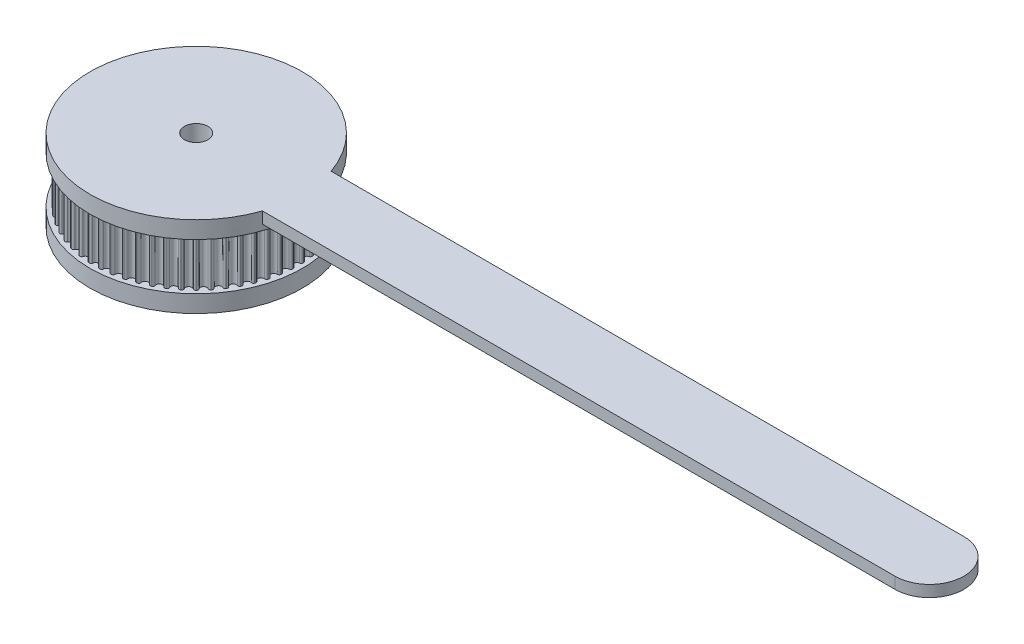
SolidWorks part; units mm, degrees
ref_plane "Front Plane" through (0, 0, 0) normal (0, 0, 1) x (1, 0, 0)
ref_plane "Top Plane" through (0, 0, 0) normal (0, 1, 0) x (1, 0, 0)
ref_plane "Right Plane" through (0, 0, 0) normal (1, 0, 0) x (0, 0, -1)
sketch "Sketch1" plane through (0, 0, 0) normal (0, 1, 0) x (1, 0, 0)
  line L0 (0, 0) -> (0, 28.2667) construction
  line L1 (0, 0) -> (2.9202, 27.7837) construction
  circle A0 centre (0, 0) radius 28.2667 construction
  circle A1 centre (0, 0) radius 27.0467 construction
  circle A2 centre (0, 27.9367) radius 0.89 construction
  circle A5 centre (2.9202, 27.7837) radius 0.89 construction
  arc A6 (0, 27.0467) -> (0.8804, 27.8061) centre (0, 27.9367) ccw
  arc A7 (0.8804, 27.8061) -> (1.3997, 28.2321) centre (1.3749, 27.7327) cw
  arc A8 (1.559, 28.2237) -> (2.031, 27.7458) centre (1.5314, 27.7245) cw
  arc A9 (2.8272, 26.8986) -> (2.031, 27.7458) centre (2.9202, 27.7837) cw
  arc A10 (1.3997, 28.2321) -> (1.559, 28.2237) centre (0, 0) cw
  arc A11 (0, 27.0467) -> (2.8272, 26.8986) centre (0, 0) ccw
  dimension "D1" = 56.5335
  dimension "D3" = 1.78
  dimension "D4" = 0.5
  dimension "D2" = 1.22
  dimension "D5" = 6
extrude "Boss-Extrude1" add sketch "Sketch1" along normal mid plane 13 contours A6 A11 A9 A8 A7 region at (0.001, 0, -0.0192)
ref_axis "Axis1" through (0, 3.3, 0) along (0, -1, 0)
pattern_circular "CirPattern1" count 60 over 360 about axis through (0, 3.3, 0) along (0, -1, 0) of "Boss-Extrude1"
sketch "Sketch2" plane through (0, 0, 0) normal (1, 0, 0) x (0, 0, -1)
  line L10 (0, 6.5) -> (29.4415, 6.5) construction
  line L11 (0, 6.5) -> (0, 8.0875) construction
  line L12 (0, 8.0875) -> (29.4415, 8.0875) construction
  line L15 (29.4415, 6.5) -> (29.4415, 8.0875) construction
  line L20 (0, 3.3) -> (0, -3.3) construction
  line L22 (29.4415, 8.0875) -> (0, 8.0875)
  line L23 (29.4415, 8.0875) -> (29.4415, 6.5)
  line L24 (29.4415, 6.5) -> (0, 6.5)
  line L25 (0, 8.0875) -> (0, 6.5)
  dimension "D1" = 1.5875
  dimension "D2" = 29.4415
  dimension "D3" = 6.5
revolve "Revolve3" add sketch "Sketch2" angle 360 about axis through (0, 3.3, 0) along (0, -1, 0) region at (0, 7.2937, -14.7207)
mirror "Mirror1" about plane through (0, 0, 0) normal (0, 1, 0) of "Revolve3"
sketch "Sketch7" plane through (0, 8.0875, 0) normal (0, 1, 0) x (1, 0, 0)
  line L0 (0, 0) -> (203.2, 0) construction
  line L1 (27.8581, 9.525) -> (203.2, 9.525)
  line L2 (27.8581, -9.525) -> (203.2, -9.525)
  arc A1 (203.2, -9.525) -> (203.2, 9.525) centre (203.2, 0) ccw
  arc A2 (27.8581, 9.525) -> (27.8581, -9.525) centre (0, 0) ccw
  circle A3 centre (0, 0) radius 29.4415 construction
  point P3 (101.6, 0)
  dimension "D1" = 203.2
  dimension "D2" = 19.05
extrude "Boss-Extrude4" add sketch "Sketch7" along normal blind 3.175
sketch "Sketch8" plane through (0, -8.0875, 0) normal (0, -1, 0) x (1, 0, 0)
  circle A0 centre (0, 0) radius 29.4415
  circle A1 centre (0, 0) radius 29.4415 construction
extrude "Boss-Extrude5" add sketch "Sketch8" along normal blind 3.175
sketch "Sketch9" plane through (0, -11.2625, 0) normal (0, -1, 0) x (1, 0, 0)
  circle A0 centre (0, 0) radius 3.2385
  dimension "D1" = 6.477
extrude "Cut-Extrude1" cut sketch "Sketch9" against normal through all both and the other way through all
equation "\"TEETH_NUM\"= 60"
equation "\"TOOTH_PITCH\"= 3mm"
equation "\"PITCH_LINE_OFFSET\"= .015in"
equation "\"DIAMETER_PER_GROOVE\"= \"OUTSIDE_DIAMETER\" / \"TEETH_NUM\" * 1in"
equation "\"PITCH_DIAMETER\"= ( ( \"TEETH_NUM\" * 3 - 1.31 ) / 3.1415 + .415 ) * 1mm"
equation "\"OUTSIDE_DIAMETER\"= \"PITCH_DIAMETER\" - \"PITCH_LINE_OFFSET\" * 2"
equation "\"D1@Sketch1\"=\"OUTSIDE_DIAMETER\""
equation "\"TOOTH_HEIGHT\"= 1.22mm"
equation "\"D2@Sketch1\"=\"TOOTH_HEIGHT\""
equation "\"TOOTH_DIAMETER\"= 1.78mm"
equation "\"INTERNAL_RADIUS\"= .5mm"
equation "\"D3@Sketch1\"=\"TOOTH_DIAMETER\""
equation "\"D5@Sketch1\"=360 / \"TEETH_NUM\""
equation "\"D4@Sketch1\"=\"INTERNAL_RADIUS\""
equation "\"D1@CirPattern1\"=\"TEETH_NUM\""
equation "\"BELT_GAP\"= 13mm"
equation "\"D2@Sketch2\"=\"PITCH_DIAMETER\"/2+1/32"
equation "\"D3@Sketch2\"=\"BELT_GAP\"/2"
equation "\"D1@Boss-Extrude1\"=\"BELT_GAP\""
